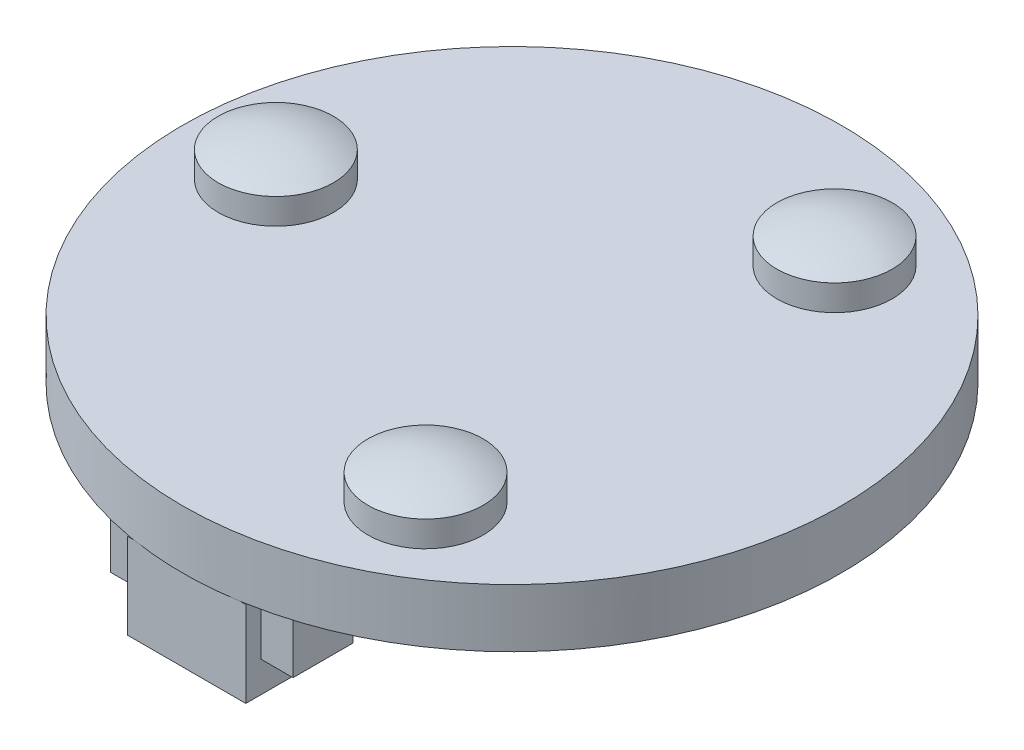
SolidWorks part; units mm, degrees
ref_plane "Front Plane" through (0, 0, 0) normal (0, 0, 1) x (1, 0, 0)
ref_plane "Top Plane" through (0, 0, 0) normal (0, 1, 0) x (1, 0, 0)
ref_plane "Right Plane" through (0, 0, 0) normal (1, 0, 0) x (0, 0, -1)
sketch "Sketch1" plane through (0, 0, 0) normal (0, 1, 0) x (1, 0, 0)
  circle A0 centre (0, 0) radius 15.35
  dimension "D1" = 30.7
extrude "Boss-Extrude1" add sketch "Sketch1" along normal blind 2.71
sketch "Sketch2" plane through (0, 2.71, 0) normal (0, 1, 0) x (-1, 0, 0)
  line L1 (-5.5, 9.5263) -> (0, 0) construction
  line L2 (0, 3.3605) -> (0, -3.3605) construction
  circle A0 centre (-5.5, 9.5263) radius 2.685
  dimension "D1" = 5.37
  dimension "D2" = 11
  dimension "D3" = 30
extrude "Boss-Extrude2" add sketch "Sketch2" along normal blind 1.2
dome "Dome1" faces to dome 1 distance 0.6 reverse direction no elliptical dome no face at (5.5, 3.91, 12.2113) parameters "D1"=0.6
pattern_circular "CirPattern1" count 3 over 360 about axis through (0, 2.71, 0) along (0, 1, 0) of "Dome1", "Boss-Extrude2"
sketch "Sketch3" plane through (0, 0, 0) normal (0, -1, 0) x (1, 0, 0)
  line L0 (0, 15.35) -> (0, -15.35) construction
  line L2 (2.75, 15.15) -> (-2.75, 15.15)
  line L3 (2.75, 15.15) -> (2.75, 10.95)
  line L4 (2.75, 10.95) -> (-2.75, 10.95)
  line L5 (-2.75, 15.15) -> (-2.75, 10.95)
  line L6 (2.75, 15.15) -> (-2.75, 10.95) construction
  line L7 (2.75, 10.95) -> (-2.75, 15.15) construction
  line L8 (-2.75, 13.05) -> (4.4429, 13.05) construction
  line L9 (2.75, 14.45) -> (4.25, 14.45)
  line L10 (4.25, 14.45) -> (4.25, 11.65)
  line L11 (4.25, 11.65) -> (2.75, 11.65)
  line L12 (-4.25, 11.65) -> (-2.75, 11.65)
  line L13 (-4.25, 14.45) -> (-4.25, 11.65)
  line L14 (-2.75, 14.45) -> (-4.25, 14.45)
  line L15 (0, 0) -> (-15.35, 0) construction
  line L16 (2.75, -14.45) -> (4.25, -14.45)
  line L17 (4.25, -14.45) -> (4.25, -11.65)
  line L18 (4.25, -11.65) -> (2.75, -11.65)
  line L19 (2.75, -15.15) -> (2.75, -10.95)
  line L20 (2.75, -10.95) -> (-2.75, -10.95)
  line L21 (-4.25, -11.65) -> (-2.75, -11.65)
  line L22 (-4.25, -14.45) -> (-4.25, -11.65)
  line L23 (-2.75, -14.45) -> (-4.25, -14.45)
  line L24 (-2.75, -15.15) -> (-2.75, -10.95)
  line L25 (2.75, -15.15) -> (-2.75, -15.15)
  line L26 (-1.5955, 10.95) -> (-1.5955, 0) construction
  line L27 (-1.5955, 0) -> (-1.5955, -10.95) construction
  point P4 (0, 13.05)
  point P16 (4.25, 13.05)
  circle M1 centre (0, 0) radius 15.35
  dimension "D1" = 5.5
  dimension "D3" = 4.2
  dimension "D4" = 2.8
  dimension "D5" = 1.5
  dimension "D6" = 21.9
extrude "Boss-Extrude3" add sketch "Sketch3" along normal blind 2.55 contours L2 L5 L4 L3 | L25 L19 L20 L24 | L11 L10 L9 L3 | L5 L14 L13 L12 | L19 L16 L17 L18 | L23 L24 L21 L22 | L3 L2 M1 | L2 L5 M1 | L25 L24 M1 | L25 L19 M1 region at (2.6575, 0, 15.134) region at (0, 0, 13.0488) region at (-2.6575, 0, 15.134) region at (3.5, 0, 13.05) region at (0, 0, -13.0488) region at (2.6575, 0, -15.134) region at (-3.5, 0, 13.05) region at (-2.6575, 0, -15.134) region at (3.5, 0, -13.05) region at (-3.5, 0, -13.05)
sketch "Sketch4" plane through (0, -2.55, 0) normal (0, -1, 0) x (1, 0, 0)
  line L0 (2.75, 10.95) -> (-2.75, 10.95) construction
  line L1 (2.75, 15.15) -> (-2.75, 15.15) construction
  line L2 (2.75, 10.95) -> (-2.75, 10.95)
  line L3 (2.75, 15.15) -> (-2.75, 15.15)
  line L4 (2.75, 15.15) -> (2.75, 10.95)
  line L5 (-2.75, 10.95) -> (-2.75, 15.15)
  line L6 (2.75, -15.15) -> (2.75, -10.95)
  line L7 (2.75, -10.95) -> (-2.75, -10.95)
  line L8 (-2.75, -10.95) -> (-2.75, -15.15)
  line L9 (-2.75, -15.15) -> (2.75, -15.15)
  line L10 (2.75, -15.15) -> (2.7698, -15.1661)
  line M2 (-2.75, 15.15) -> (-2.75, 14.45)
  line M6 (-2.75, 11.65) -> (-2.75, 10.95)
  line M7 (-2.75, 10.95) -> (2.75, 10.95)
  line M8 (2.75, 10.95) -> (2.75, 11.65)
  line M12 (2.75, 14.45) -> (2.75, 15.15)
  line M14 (2.75, 15.15) -> (-2.75, 15.15)
extrude "Boss-Extrude4" add sketch "Sketch4" along normal blind 1.44 contours L5 L4 M6 M7 M8 M12 M14 M2 | L8 L9 L6 L7 region at (0, -2.55, 13.05) region at (0, -2.55, -13.05)
move or copy body "Body-Move/Copy1" [suppressed] bodies to move or copy 106
